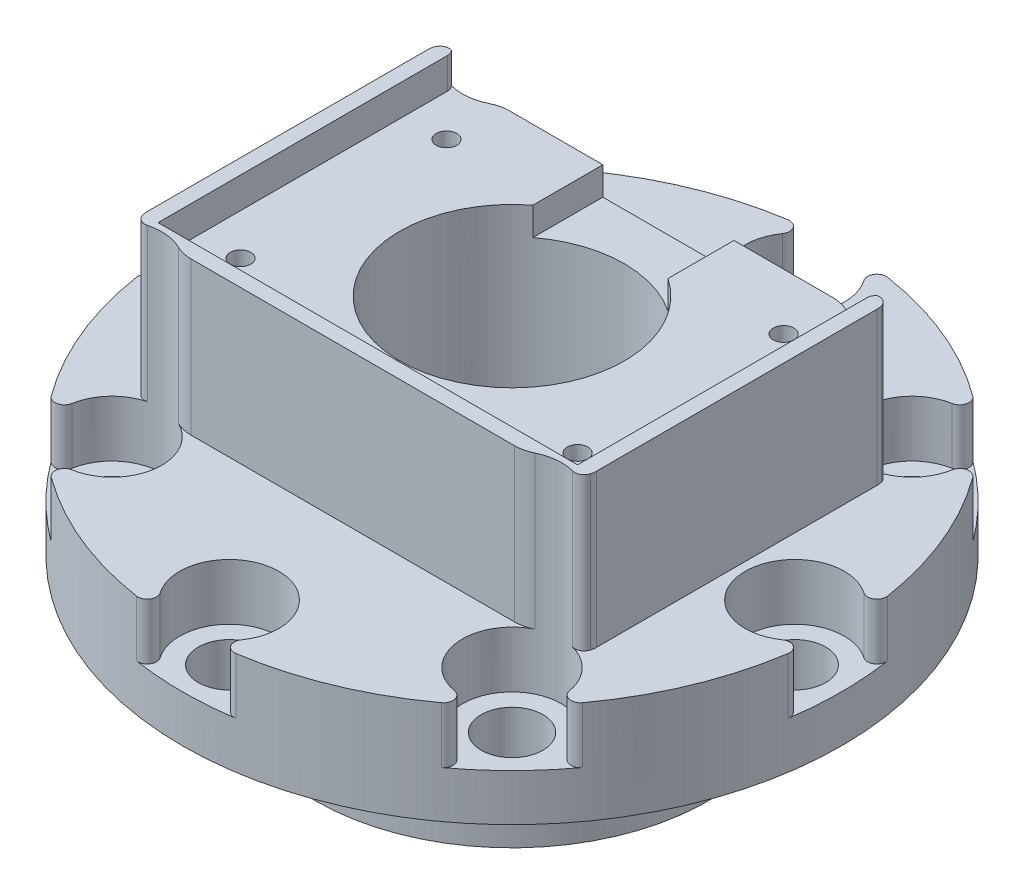
SolidWorks part; units mm, degrees
ref_plane "Front Plane" through (0, 0, 0) normal (0, 0, 1) x (1, 0, 0)
ref_plane "Top Plane" through (0, 0, 0) normal (0, 1, 0) x (1, 0, 0)
ref_plane "Right Plane" through (0, 0, 0) normal (1, 0, 0) x (0, 0, -1)
ref_plane "Plane1" through (0, 18.1, 0) normal (0, -1, 0) x (-1, 0, 0)
ref_plane "Plane2" through (0, 6.1, 0) normal (0, 1, 0) x (1, 0, 0)
sketch "Sketch1" plane through (0, 18.1, 0) normal (0, -1, 0) x (-1, 0, 0)
  line L0 (-10, 18.7) -> (10, 18.7) construction
  line L1 (-10, 18.7) -> (-10, 13.7) construction
  line L2 (10, 18.7) -> (10, 13.7) construction
  line L3 (-10, 13.7) -> (10, 13.7) construction
  line L4 (11, -7.5) -> (11, 20.5)
  line L5 (11, 20.5) -> (-11, 20.5)
  line L6 (5.2, 11.5) -> (-3.35, 11.5)
  line L7 (-3.35, 11.5) -> (-3.35, 4.5)
  line L8 (-3.35, 4.5) -> (3.65, 4.5)
  line L9 (3.65, 4.5) -> (3.65, 9)
  line L10 (3.65, 9) -> (5.2, 9)
  line L11 (5.2, 9) -> (5.2, 11.5)
  line L12 (5.2, 11.5) -> (-3.35, 11.5)
  line L13 (-3.35, 11.5) -> (-3.35, 4.5)
  line L14 (-3.35, 4.5) -> (3.65, 4.5)
  line L15 (3.65, 4.5) -> (3.65, 9)
  line L16 (3.65, 9) -> (5.2, 9)
  line L17 (5.2, 9) -> (5.2, 11.5)
  line L18 (-11, 20.5) -> (-11, -7.5)
  line L19 (-11, -7.5) -> (11, -7.5)
  line L20 (11, -7.5) -> (11, 20.5)
  line L21 (11, 20.5) -> (-11, 20.5)
  line L22 (-11, 20.5) -> (-11, -7.5)
  line L23 (-11, -7.5) -> (11, -7.5)
  line L24 (-2.58, -2.15) -> (2.58, -2.15)
  line L25 (-2.58, 2.15) -> (-2.58, -2.15)
  line L26 (2.58, 2.15) -> (-2.58, 2.15)
  line L27 (2.58, -2.15) -> (2.58, 2.15)
  line L28 (-2.58, -2.15) -> (2.58, -2.15)
  line L29 (-2.58, 2.15) -> (-2.58, -2.15)
  line L30 (2.58, 2.15) -> (-2.58, 2.15)
  line L31 (2.58, -2.15) -> (2.58, 2.15)
  line L32 (-10, 18.7) -> (10, 18.7)
  line L33 (-10, 18.7) -> (-10, 13.7)
  line L34 (10, 18.7) -> (10, 13.7)
  line L35 (-10, 13.7) -> (10, 13.7)
  circle A0 centre (-9, 5.5) radius 1.3 construction
  circle A1 centre (-9, -5.5) radius 1.3 construction
  circle A2 centre (9, -5.5) radius 1.3 construction
  circle A3 centre (9, 5.5) radius 1.3 construction
  circle A4 centre (-9, 5.5) radius 1.3
  circle A5 centre (-9, -5.5) radius 1.3
  circle A6 centre (9, -5.5) radius 1.3
  circle A7 centre (9, 5.5) radius 1.3
  dimension "D1" = 0
  dimension "D2" = 0
  dimension "D3" = 0
sketch "Sketch2" plane through (0, 6.1, 0) normal (0, 1, 0) x (1, 0, 0)
  line L0 (0, -12.6) -> (0, -17.6) construction
  arc A0 (-17.6, 0) -> (17.6, 0) centre (0, 0) ccw construction
  arc A1 (-17.6, 0) -> (17.6, 0) centre (0, 0) ccw construction
  circle A2 centre (0, 0) radius 12.6 construction
  circle A3 centre (0, 0) radius 12.6 construction
  circle A4 centre (0, 0) radius 17.6
  circle A5 centre (0, 0) radius 6
  circle A6 centre (0, -15.1) radius 1.65
  circle A7 centre (0, -15.1) radius 1.65 construction
  circle A8 centre (-10.6773, -10.6773) radius 1.65
  circle A9 centre (-15.1, 0) radius 1.65
  circle A10 centre (-10.6773, 10.6773) radius 1.65
  circle A11 centre (0, 15.1) radius 1.65
  circle A12 centre (10.6773, 10.6773) radius 1.65
  circle A13 centre (15.1, 0) radius 1.65
  circle A14 centre (10.6773, -10.6773) radius 1.65
  dimension "D1" = 12
sketch "Sketch3" plane through (0, 0, 0) normal (0, 1, 0) x (1, 0, 0)
  circle A0 centre (0, 0) radius 8.49
  circle A1 centre (0, 0) radius 8.49 construction
  circle A2 centre (0, 0) radius 10.49
  dimension "D1" = 2
extrude "Boss-Extrude1" add sketch "Sketch2" along normal blind 2.5
extrude "Boss-Extrude2" add sketch "Sketch3" along normal up to surface (6.1 mm away) up to face at (0, 6.1, 17.6)
sketch "Sketch4" plane through (0, 8.6, 0) normal (0, 1, 0) x (1, 0, 0)
  circle A0 centre (0, 0) radius 12.6 construction
  circle A1 centre (0, 0) radius 12.6
sketch "Sketch5" plane through (0, 18.1, 0) normal (0, -1, 0) x (-1, 0, 0)
  line L0 (11, -7.5) -> (11, 20.5) construction
  line L1 (-11, 20.5) -> (-11, -7.5) construction
  line L2 (-11, -7.5) -> (11, -7.5) construction
  line L3 (11, -7.5) -> (11, 20.5) construction
  line L4 (-11, 20.5) -> (-11, -7.5) construction
  line L5 (-11, -7.5) -> (11, -7.5) construction
  line L6 (-12, 7.5) -> (-12, -7.5)
  line L7 (-11, -8.5) -> (11, -8.5)
  line L8 (12, -7.5) -> (12, 7.5)
  line L9 (-12, -8.5) -> (12, -8.5) construction
  line L10 (12, -8.5) -> (12, 20.5) construction
  line L11 (-12, 20.5) -> (-12, -8.5) construction
  line L12 (11, 8.5) -> (-11, 8.5)
  line L13 (9, -6.8) -> (9, -8.5) construction
  line L14 (9, 6.8) -> (9, 8.5) construction
  circle A0 centre (9, -5.5) radius 1.3 construction
  circle A1 centre (0, 0) radius 12.6
  circle A2 centre (0, 0) radius 12.6 construction
  circle A3 centre (9, 5.5) radius 1.3 construction
  circle A4 centre (-9, -5.5) radius 1.3 construction
  circle A5 centre (-9, 5.5) radius 1.3 construction
  circle A6 centre (9, -5.5) radius 1.3 construction
  circle A7 centre (9, 5.5) radius 1.3 construction
  circle A8 centre (-9, -5.5) radius 1.3 construction
  circle A9 centre (-9, 5.5) radius 1.3 construction
  arc A10 (11, -8.5) -> (12, -7.5) centre (11, -7.5) ccw
  arc A11 (-11, -8.5) -> (-12, -7.5) centre (-11, -7.5) cw
  circle A13 centre (0, 0) radius 6 construction
  circle A14 centre (0, 0) radius 6
  arc A15 (12, 7.5) -> (11, 8.5) centre (11, 7.5) ccw
  arc A16 (-11, 8.5) -> (-12, 7.5) centre (-11, 7.5) ccw
  point P25 (0, 8.5)
  dimension "D3" = 1
  dimension "D4" = 1
  dimension "D1" = 0
  dimension "D2" = 1
extrude "Boss-Extrude3" add sketch "Sketch5" along normal up to surface (9.5 mm away) up to face at (15.1, 8.6, 1.65)
sketch "Sketch6" plane through (0, 18.1, 0) normal (0, 1, 0) x (1, 0, 0)
  line L0 (11, -7.5) -> (-11, -7.5) construction
  line L1 (-11, -7.5) -> (-11, 20.5) construction
  line L2 (11, 20.5) -> (11, -7.5) construction
  line L3 (11, -7.5) -> (-11, -7.5) construction
  line L4 (11, 8.5) -> (-11, 8.5)
  line L5 (-12, 7.5) -> (-12, -7.5)
  line L6 (-11, -8.5) -> (11, -8.5)
  line L7 (12, -7.5) -> (12, 7.5)
  line L9 (-12, 7.5) -> (-12, -7.5)
  line L10 (-11, -8.5) -> (11, -8.5)
  line L11 (12, -7.5) -> (12, 7.5)
  line L12 (-11, -7.5) -> (-11, 20.5) construction
  line L13 (11, 20.5) -> (11, -7.5) construction
  line L14 (11.2, 8.4798) -> (11.2, -7.7)
  line L15 (11.2, -7.7) -> (-11.2, -7.7)
  line L16 (-11.2, -7.7) -> (-11.2, 8.4798)
  line L17 (11.2, 20.5) -> (11.2, -7.7) construction
  line L18 (-11.2, -7.7) -> (-11.2, 20.5) construction
  arc A6 (12, 7.5) -> (11, 8.5) centre (11, 7.5) ccw
  arc A7 (-11, 8.5) -> (-12, 7.5) centre (-11, 7.5) ccw
  arc A8 (-12, -7.5) -> (-11, -8.5) centre (-11, -7.5) ccw
  arc A9 (11, -8.5) -> (12, -7.5) centre (11, -7.5) ccw
  arc A10 (12, 7.5) -> (11.2, 8.4798) centre (11, 7.5) ccw
  arc A11 (-11.2, 8.4798) -> (-12, 7.5) centre (-11, 7.5) ccw
  arc A12 (-12, -7.5) -> (-11, -8.5) centre (-11, -7.5) ccw
  arc A13 (11, -8.5) -> (12, -7.5) centre (11, -7.5) ccw
  dimension "D2" = 0
  dimension "D3" = 0.2
extrude "Boss-Extrude4" add sketch "Sketch6" along normal blind 1.65
sketch "Sketch7" plane through (0, 8.6, 0) normal (0, 1, 0) x (1, 0, 0)
  circle A0 centre (10.6773, 10.6773) radius 2.65
  circle A1 centre (-10.6773, 10.6773) radius 2.65
  circle A2 centre (-10.6773, -10.6773) radius 2.65
  circle A3 centre (10.6773, -10.6773) radius 2.65
  dimension "D1" = 5.3
extrude "Cut-Extrude1" cut sketch "Sketch7" along normal through all
sketch "Sketch8" plane through (0, 8.6, 0) normal (0, 1, 0) x (1, 0, 0)
  circle A0 centre (0, 0) radius 17.6 construction
  arc A1 (0.9485, -17.5744) -> (11.7563, -13.0977) centre (0, 0) ccw
  arc A2 (-0.9485, 17.5744) -> (0.9485, 17.5744) centre (0, 15.1) ccw
  circle A3 centre (10.6773, -10.6773) radius 2.65
  arc A4 (13.0977, -11.7563) -> (11.7563, -13.0977) centre (10.6773, -10.6773) ccw
  circle A5 centre (-10.6773, -10.6773) radius 2.65
  arc A6 (-11.7563, -13.0977) -> (-13.0977, -11.7563) centre (-10.6773, -10.6773) ccw
  circle A7 centre (-10.6773, 10.6773) radius 2.65
  arc A8 (-13.0977, 11.7563) -> (-11.7563, 13.0977) centre (-10.6773, 10.6773) ccw
  circle A9 centre (10.6773, 10.6773) radius 2.65
  arc A10 (11.7563, 13.0977) -> (13.0977, 11.7563) centre (10.6773, 10.6773) ccw
  arc A11 (-17.5744, -0.9485) -> (-17.5744, 0.9485) centre (-15.1, 0) ccw
  arc A12 (0.9485, -17.5744) -> (-0.9485, -17.5744) centre (0, -15.1) ccw
  arc A13 (17.5744, 0.9485) -> (17.5744, -0.9485) centre (15.1, 0) ccw
  arc A14 (13.0977, -11.7563) -> (17.5744, -0.9485) centre (0, 0) ccw
  arc A15 (17.5744, 0.9485) -> (13.0977, 11.7563) centre (0, 0) ccw
  arc A16 (11.7563, 13.0977) -> (0.9485, 17.5744) centre (0, 0) ccw
  arc A17 (-0.9485, 17.5744) -> (-11.7563, 13.0977) centre (0, 0) ccw
  arc A18 (-13.0977, 11.7563) -> (-17.5744, 0.9485) centre (0, 0) ccw
  arc A19 (-17.5744, -0.9485) -> (-13.0977, -11.7563) centre (0, 0) ccw
  arc A20 (-11.7563, -13.0977) -> (-0.9485, -17.5744) centre (0, 0) ccw
  circle A21 centre (0, 0) radius 6 construction
  circle A22 centre (0, 0) radius 6
  dimension "D1" = 0
  dimension "D2" = 0
  dimension "D3" = 0
  dimension "D4" = 0
extrude "Boss-Extrude5" add sketch "Sketch8" along normal blind 3
fillet "Fillet2" radius 0.5 20 edges at (11.6866, 15.675, 8.227) (-11.6866, 15.675, 8.227) (-11.6866, 15.675, -8.227) (11.6866, 15.675, -8.227) (17.5744, 10.1, -0.9485) (-13.0977, 10.1, 11.7563) (11.7563, 10.1, -13.0977) (0.9485, 10.1, -17.5744) (-0.9485, 10.1, -17.5744) (-11.7563, 10.1, -13.0977) (-13.0977, 10.1, -11.7563) (-17.5744, 10.1, -0.9485) (-17.5744, 10.1, 0.9485) (-11.7563, 10.1, 13.0977) (-0.9485, 10.1, 17.5744) (0.9485, 10.1, 17.5744) (13.0977, 10.1, 11.7563) (11.7563, 10.1, 13.0977) (17.5744, 10.1, 0.9485) (13.0977, 10.1, -11.7563)
fillet "Fillet3" radius 0.5 2 edges at (-11.2, 18.925, -8.0794) (11.2, 18.925, -8.0794)
fillet "Fillet4" radius 2 4 edges at (9.1667, 15.675, 8.5) (-9.1667, 15.675, 8.5) (-9.1667, 14.85, -8.5) (9.1667, 14.85, -8.5)
chamfer "Chamfer1" distance 0.5 angle 45 1 edges at (0, 0, 8.49)
sketch "Sketch9" plane through (0, 18.1, 0) normal (0, 1, 0) x (1, 0, 0)
  circle A0 centre (9, -5.5) radius 0.55
  circle A1 centre (-9, -5.5) radius 0.55
  circle A2 centre (-9, 5.5) radius 0.55
  circle A3 centre (9, 5.5) radius 0.55
  dimension "D1" = 1.1
extrude "Cut-Extrude2" cut sketch "Sketch9" against normal blind 5
sketch "Sketch10" plane through (0, 6.1, 0) normal (0, -1, 0) x (1, 0, 0)
  circle A1 centre (0, 0) radius 8.49
  circle A2 centre (0, 0) radius 8.49
  dimension "D1" = 0
extrude "Cut-Extrude4" cut sketch "Sketch10" against normal blind 0.3
sketch "Sketch11" plane through (0, 18.1, 0) normal (0, 1, 0) x (1, 0, 0)
  line L0 (-5.2, 9) -> (-5.2, 11.5) construction
  line L1 (-3.65, 9) -> (-5.2, 9) construction
  line L2 (3.35, 11.5) -> (3.35, 4.5) construction
  line L3 (3.35, 4.5) -> (-3.65, 4.5) construction
  line L4 (-3.65, 4.5) -> (-3.65, 9) construction
  line L5 (-5.2, 11.5) -> (3.35, 11.5) construction
  line L6 (-5.2, 9) -> (-5.2, 11.5)
  line L7 (-3.65, 9) -> (-5.2, 9)
  line L8 (3.35, 11.5) -> (3.35, 4.5)
  line L9 (3.35, 4.5) -> (-3.65, 4.5)
  line L10 (-3.65, 4.5) -> (-3.65, 9)
  line L11 (-5.2, 11.5) -> (3.35, 11.5)
extrude "Cut-Extrude5" cut sketch "Sketch11" against normal blind 1.5
